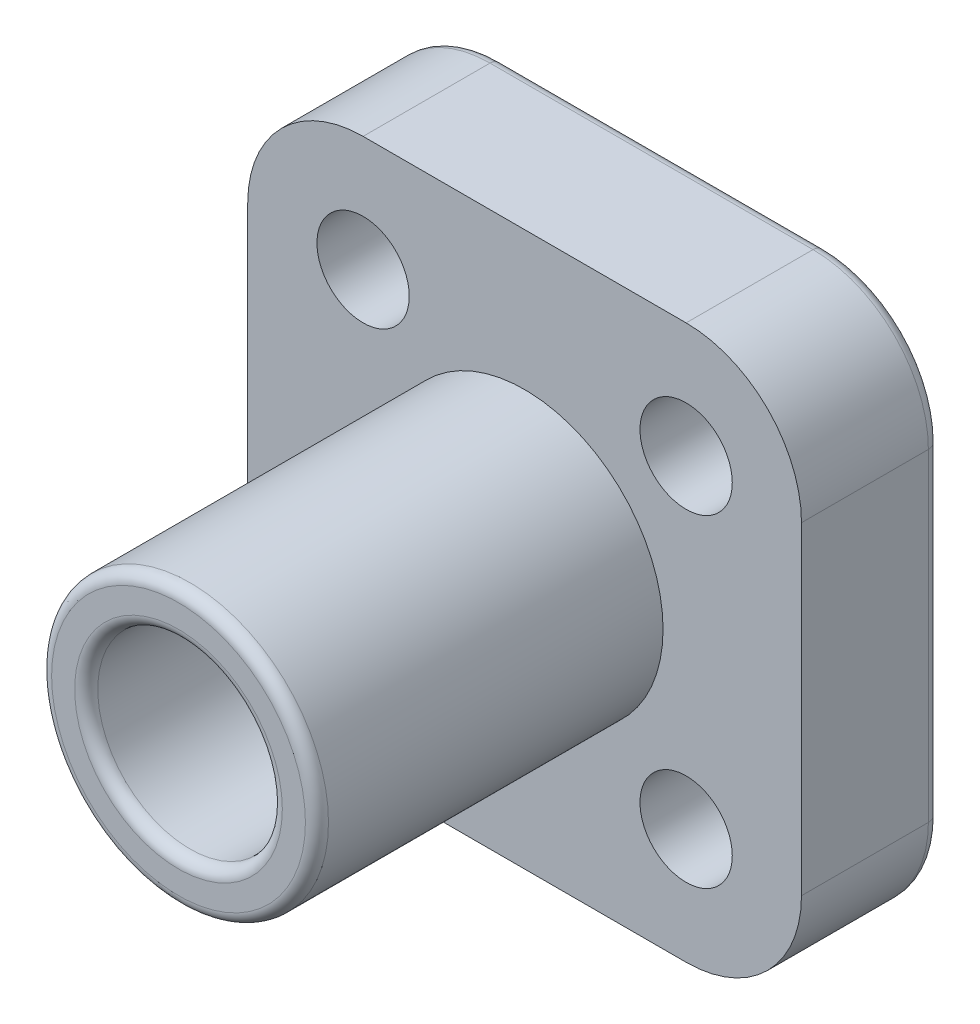
SolidWorks part; units mm, degrees
ref_plane "Plan de face" through (0, 0, 0) normal (0, 0, 1) x (1, 0, 0)
ref_plane "Plan de dessus" through (0, 0, 0) normal (0, 1, 0) x (1, 0, 0)
ref_plane "Plan de droite" through (0, 0, 0) normal (1, 0, 0) x (0, 0, -1)
sketch "Esquisse1" plane through (0, 0, 0) normal (0, 0, 1) x (1, 0, 0)
  line L0 (-7, 7) -> (7, 7) construction
  line L1 (7, -12) -> (-7, -12)
  line L2 (12, -7) -> (12, 7)
  line L3 (7, 12) -> (-7, 12)
  line L4 (-12, -7) -> (-12, 7)
  line L5 (12, -12) -> (-12, 12) construction
  line L6 (12, 12) -> (-12, -12) construction
  line L7 (-7, 7) -> (-7, -7) construction
  arc A0 (7, -12) -> (12, -7) centre (7, -7) ccw
  arc A1 (-7, -12) -> (-12, -7) centre (-7, -7) cw
  arc A2 (12, 7) -> (7, 12) centre (7, 7) ccw
  arc A3 (-7, 12) -> (-12, 7) centre (-7, 7) ccw
  circle A4 centre (-7, 7) radius 2
  circle A5 centre (7, 7) radius 2
  circle A6 centre (7, -7) radius 2
  circle A7 centre (-7, -7) radius 2
  point P0 (0, 0)
  dimension "D2" = 5
  dimension "D3" = 4
  dimension "D1" = 14
  dimension "D6" = 14
  dimension "D7" = 14
  dimension "D4" = 2
  dimension "D5" = 2
extrude "Boss.-Extru.1" add sketch "Esquisse1" along normal blind 6
sketch "Esquisse2" plane through (0, 0, 6) normal (0, 0, 1) x (1, 0, 0)
  circle A0 centre (0, 0) radius 6
  circle A1 centre (0, 0) radius 4
  dimension "D1" = 8
  dimension "D2" = 12
extrude "Boss.-Extru.2" add sketch "Esquisse2" along normal blind 15 contours A0 | A1
sketch "Esquisse3" plane through (0, 0, 6) normal (0, 0, 1) x (1, 0, 0)
  circle A0 centre (0, 0) radius 4
extrude "Enlèv. mat.-Extru.1" cut sketch "Esquisse3" against normal up to next
fillet "Congé1" radius 0.5 15 edges at (6, 0, 21) (4, 0, 21) (-5, -7, 0) (9, -7, 0) (9, 7, 0) (-5, 7, 0) (12, 0, 0) (10.5355, 10.5355, 0) (0, 12, 0) (-10.5355, 10.5355, 0) (-12, 0, 0) (-10.5355, -10.5355, 0) (0, -12, 0) (10.5355, -10.5355, 0) (4, 0, 0)
